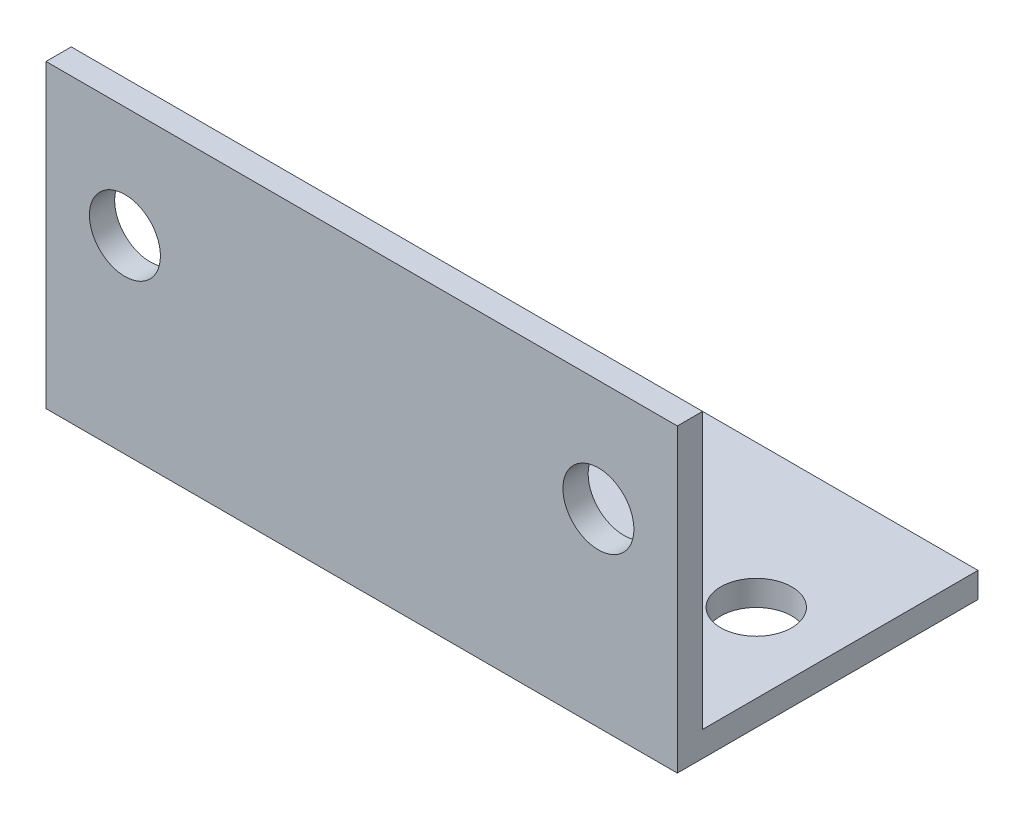
SolidWorks part; units mm, degrees
ref_plane "Front Plane" through (0, 0, 0) normal (0, 0, 1) x (1, 0, 0)
ref_plane "Top Plane" through (0, 0, 0) normal (0, 1, 0) x (1, 0, 0)
ref_plane "Right Plane" through (0, 0, 0) normal (1, 0, 0) x (0, 0, -1)
sketch "Sketch1" plane through (0, 0, 0) normal (1, 0, 0) x (0, 0, -1)
  line L0 (0, 0) -> (0, 19.05)
  line L1 (0, 19.05) -> (1.6, 19.05)
  line L2 (1.6, 19.05) -> (1.6, 1.6)
  line L3 (1.6, 1.6) -> (19.05, 1.6)
  line L4 (19.05, 1.6) -> (19.05, 0)
  line L5 (19.05, 0) -> (0, 0)
  dimension "D1" = 1.6
  dimension "D2" = 1.6
  dimension "D3" = 19.05
  dimension "D4" = 19.05
extrude "Boss-Extrude1" add sketch "Sketch1" along normal mid plane 40
hole_wizard "M4 Clearance Hole1" positions "Sketch4" profile "Sketch3" hole size "M4" standard "ANSI Metric" end condition through all
sketch "Sketch4" plane through (0, 0, 0) normal (0, 0, 1) x (1, 0, 0)
  line L0 (20, 0) -> (-20, 0) construction
  point P0 (-15, 12)
  point P2 (15, 12)
  point P7 (0, 0)
  dimension "D1" = 12
  dimension "D2" = 15
  dimension "D3" = 15
sketch "Sketch3" plane through (-15, 12, 0) normal (1, 0, 0) x (0, -1, 0)
  line L0 (0, 0) -> (0, 19.05)
  line L1 (0, 19.05) -> (2.25, 19.05)
  line L2 (2.25, 19.05) -> (2.25, 0)
  line L5 (2.25, 0) -> (0, 0)
  line L11 (0, -6.35) -> (0, 107.95) construction
  dimension "Thru Hole Dia." = 4.5
  dimension "Thru Hole Depth" = 19.05
hole_wizard "M4 Clearance Hole2" positions "Sketch8" profile "Sketch6" hole size "M4" standard "ANSI Metric" end condition through all
sketch "Sketch8" plane through (0, 0, 0) normal (0, -1, 0) x (-1, 0, 0)
  line L0 (-20, 0) -> (20, 0) construction
  point P0 (-15, 10)
  point P2 (15, 10)
  dimension "D1" = 15
  dimension "D2" = 10
  dimension "D3" = 15
sketch "Sketch6" plane through (15, 0, -10) normal (1, 0, 0) x (0, 0, -1)
  line L0 (0, 0) -> (0, 19.05)
  line L1 (0, 19.05) -> (2.25, 19.05)
  line L2 (2.25, 19.05) -> (2.25, 0)
  line L5 (2.25, 0) -> (0, 0)
  line L11 (0, -6.35) -> (0, 107.95) construction
  dimension "Thru Hole Dia." = 4.5
  dimension "Thru Hole Depth" = 19.05
